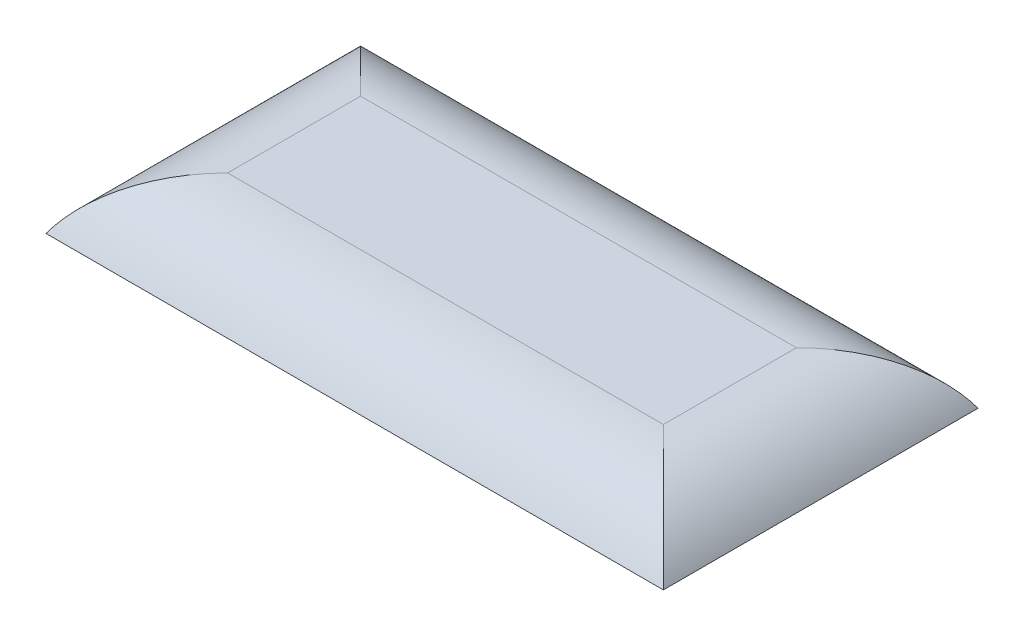
SolidWorks part; units mm, degrees
material "SANTOPRENE"
ref_plane "Front Plane" through (0, 0, 0) normal (0, 0, 1) x (1, 0, 0)
ref_plane "Top Plane" through (0, 0, 0) normal (0, 1, 0) x (1, 0, 0)
ref_plane "Right Plane" through (0, 0, 0) normal (1, 0, 0) x (0, 0, -1)
sketch "Sketch1" plane through (0, 0, 0) normal (0, 1, 0) x (1, 0, 0)
  line L1 (-45.6141, 1.6724) -> (13.2559, 1.6724)
  line L2 (-45.6141, 1.6724) -> (-45.6141, -28.3276)
  line L3 (-45.6141, -28.3276) -> (13.2559, -28.3276)
  line L4 (13.2559, 1.6724) -> (13.2559, -28.3276)
  dimension "D1" = 58.87
  dimension "D2" = 30
extrude "Boss-Extrude1" add sketch "Sketch1" along normal blind 5
fillet "Fillet1" radius 10 4 edges at (-16.1791, 5, -1.6724) (13.2559, 5, 13.3276) (-16.1791, 5, 28.3276) (-45.6141, 5, 13.3276)
